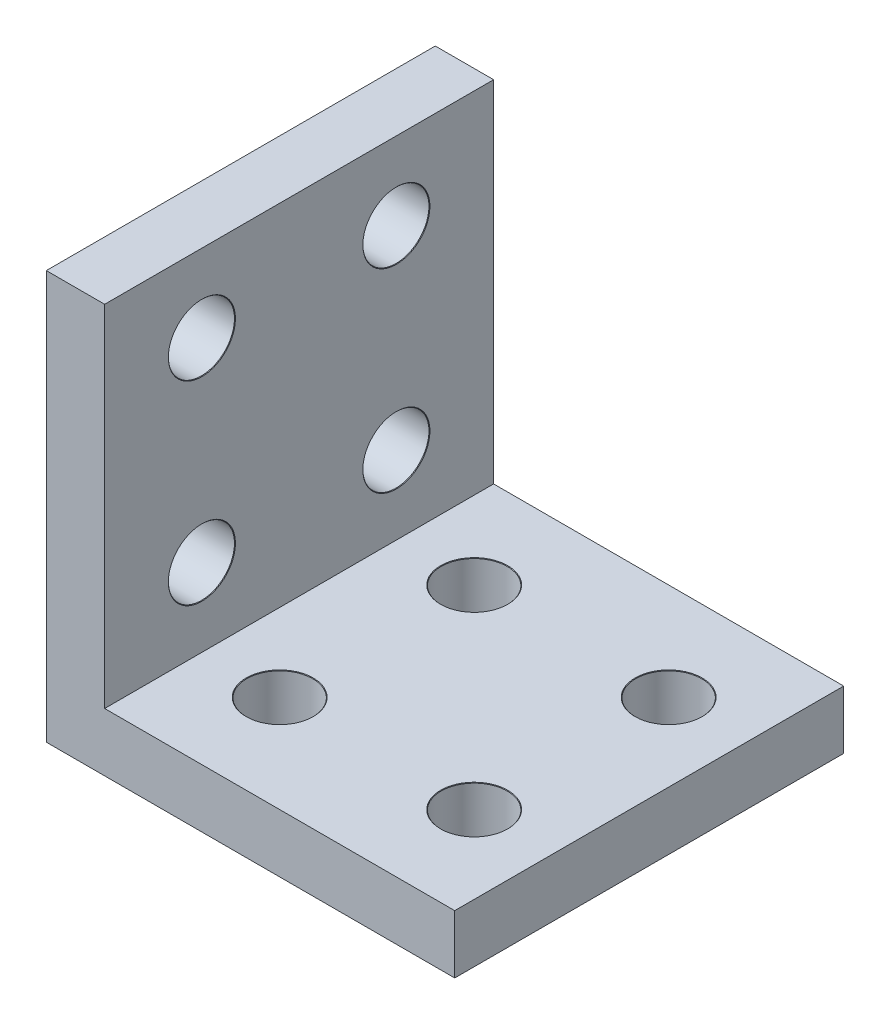
SolidWorks part; units mm, degrees
ref_plane "Front Plane" through (0, 0, 0) normal (0, 0, 1) x (1, 0, 0)
ref_plane "Top Plane" through (0, 0, 0) normal (0, 1, 0) x (1, 0, 0)
ref_plane "Right Plane" through (0, 0, 0) normal (1, 0, 0) x (0, 0, -1)
sketch "Sketch1" plane through (0, 0, 0) normal (0, 0, 1) x (1, 0, 0)
  line L0 (0, 21) -> (0, 0)
  line L1 (0, 0) -> (21, 0)
  line L2 (21, 0) -> (21, 3)
  line L3 (21, 3) -> (3, 3)
  line L4 (3, 3) -> (3, 21)
  line L5 (3, 21) -> (0, 21)
  dimension "D1" = 3
  dimension "D2" = 18
extrude "Boss-Extrude1" add sketch "Sketch1" along normal blind 20
hole_wizard "M3 Clearance Hole1" positions "Sketch2" profile "Sketch3" hole size "M3" standard "ANSI Metric" end condition through all
sketch "Sketch2" plane through (0, 3, 0) normal (0, 1, 0) x (1, 0, 0)
  line L0 (3, -10) -> (21, -10) construction
  line L1 (3, -20) -> (3, 0) construction
  line L2 (21, -20) -> (21, 0) construction
  line L4 (12, 0) -> (12, -20) construction
  line L5 (21, 0) -> (3, 0) construction
  line L6 (21, -20) -> (3, -20) construction
  line L7 (7, -15) -> (17, -15) construction
  line L8 (17, -15) -> (17, -5) construction
  line L9 (17, -5) -> (7, -5) construction
  line L10 (7, -5) -> (7, -15) construction
  point P15 (7, -5)
  point P17 (17, -5)
  point P19 (17, -15)
  point P21 (7, -15)
  point P32 (17, -10)
  point P35 (12, -5)
  dimension "D1" = 10
sketch "Sketch3" plane through (7, 3, 15) normal (1, 0, 0) x (0, 0, 1)
  line L0 (0, 0) -> (0, 3)
  line L1 (0, 3) -> (1.7, 3)
  line L2 (1.7, 3) -> (1.7, 0.025)
  line L3 (1.7, 0.025) -> (1.725, 0)
  line L5 (1.725, 0) -> (0, 0)
  line L6 (-1.7, 0.025) -> (-1.725, 0) construction
  line L11 (0, -6.35) -> (0, 107.95) construction
  dimension "Thru Hole Dia." = 3.4
  dimension "Thru Hole Depth" = 3
  dimension "Near C'Sink Dia." = 3.45
  dimension "Near C'Sink Angle" = 90
hole_wizard "M3 Clearance Hole2" positions "Sketch4" profile "Sketch5" hole size "M3" standard "ANSI Metric" end condition through all
sketch "Sketch4" plane through (3, 0, 0) normal (1, 0, 0) x (0, 0, -1)
  line L0 (-15, 7) -> (-15, 17) construction
  line L1 (-15, 17) -> (-5, 17) construction
  line L2 (-5, 17) -> (-5, 7) construction
  line L3 (-5, 7) -> (-15, 7) construction
  line L5 (-10, 3) -> (-10, 21) construction
  line L6 (-20, 21) -> (0, 21) construction
  line L8 (0, 12) -> (-20, 12) construction
  line L9 (0, 3) -> (0, 21) construction
  line L10 (-20, 3) -> (-20, 21) construction
  line L12 (-20, 3) -> (0, 3) construction
  point P0 (-15, 7)
  point P2 (-5, 7)
  point P4 (-5, 17)
  point P6 (-15, 17)
  point P30 (-10, 7)
  point P34 (-5, 12)
  dimension "D1" = 10
sketch "Sketch5" plane through (3, 7, 15) normal (0, 1, 0) x (0, 0, -1)
  line L0 (0, 0) -> (0, 3)
  line L1 (0, 3) -> (1.7, 3)
  line L2 (1.7, 3) -> (1.7, 0.025)
  line L3 (1.7, 0.025) -> (1.725, 0)
  line L5 (1.725, 0) -> (0, 0)
  line L6 (-1.7, 0.025) -> (-1.725, 0) construction
  line L11 (0, -6.35) -> (0, 107.95) construction
  dimension "Thru Hole Dia." = 3.4
  dimension "Thru Hole Depth" = 3
  dimension "Near C'Sink Dia." = 3.45
  dimension "Near C'Sink Angle" = 90
